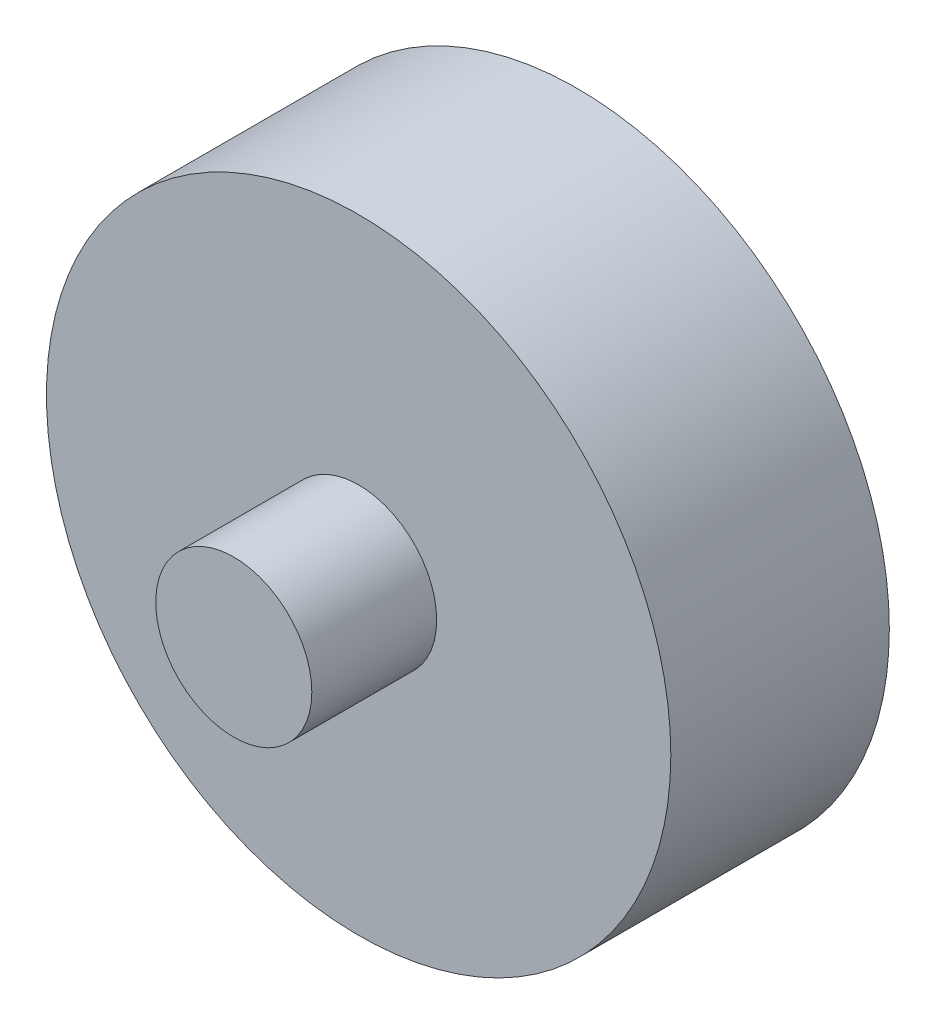
SolidWorks part; units mm, degrees
ref_plane "Front Plane" through (0, 0, 0) normal (0, 0, 1) x (1, 0, 0)
ref_plane "Top Plane" through (0, 0, 0) normal (0, 1, 0) x (1, 0, 0)
ref_plane "Right Plane" through (0, 0, 0) normal (1, 0, 0) x (0, 0, -1)
sketch "Sketch1" plane through (0, 0, 0) normal (0, 0, 1) x (1, 0, 0)
  circle A0 centre (10, 10) radius 10
  circle A1 centre (10, 10) radius 2.5
  dimension "D1" = 5
  dimension "D2" = 20
extrude "Boss-Extrude1" add sketch "Sketch1" along normal blind 11 contours A1 region at (10, 10, 0)
extrude "Boss-Extrude2" add sketch "Sketch1<3>" along normal blind 7
sketch "Sketch1<3>" plane through (0, 0, 0) normal (0, 0, 1) x (1, 0, 0) same geometry as "Sketch1"
